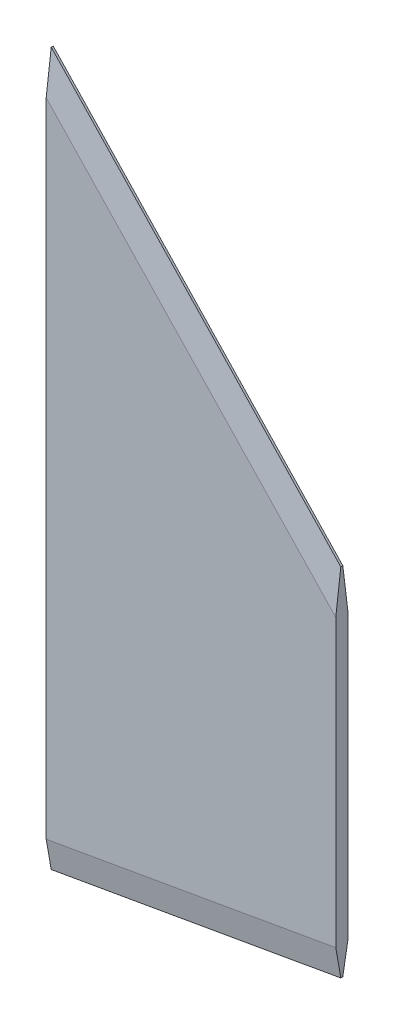
SolidWorks part; units mm, degrees
material "Hexcel AS4C (3000 Filaments)"
ref_plane "Front Plane" through (0, 0, 0) normal (0, 0, 1) x (1, 0, 0)
ref_plane "Top Plane" through (0, 0, 0) normal (0, 1, 0) x (1, 0, 0)
ref_plane "Right Plane" through (0, 0, 0) normal (1, 0, 0) x (0, 0, -1)
sketch "Sketch1" plane through (0, 0, 0) normal (0, 0, 1) x (1, 0, 0)
  line L0 (-60.9816, 109.9312) -> (-60.9816, -67.8688)
  line L1 (-60.9816, -67.8688) -> (11.3132, -55.1688)
  line L2 (11.3132, -55.1688) -> (11.3132, 33.7312)
  line L3 (11.3132, 33.7312) -> (-60.9816, 109.9312)
extrude "Boss-Extrude1" add sketch "Sketch1" along normal mid plane 3
chamfer "Chamfer1" distance 1.25 angle 80 4 edges at (-24.8342, -61.5188, -1.5) (-24.8342, -61.5188, 1.5) (-24.8342, 71.8312, -1.5) (-24.8342, 71.8312, 1.5) first distance on face at (-24.8342, -61.5188, 0) first distance on face at (-24.8342, 71.8312, 0)
